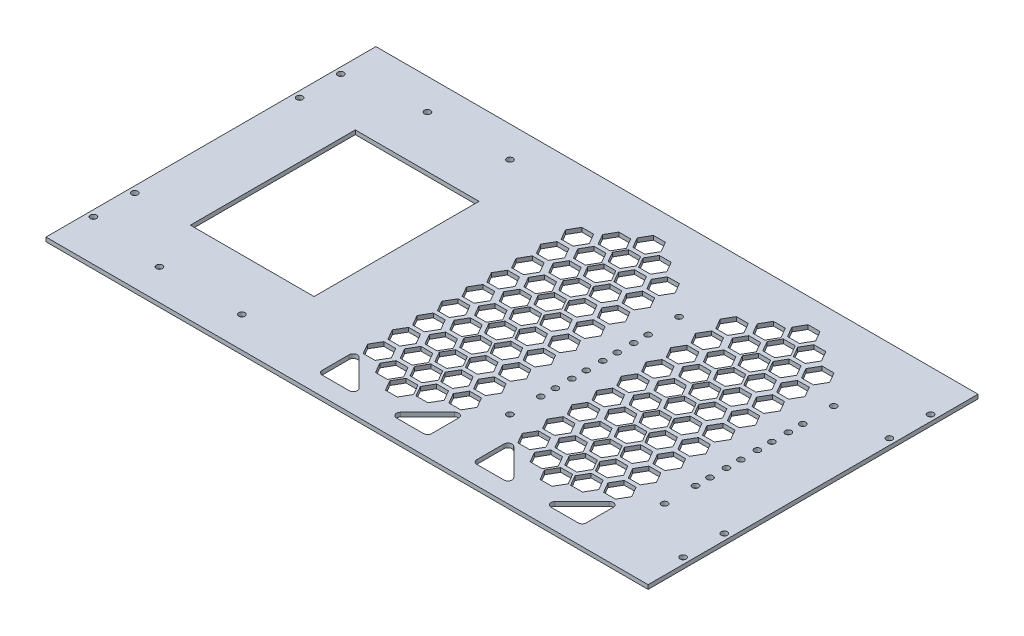
SolidWorks part; units mm, degrees
material "Thornel Mat VMA"
ref_plane "前视基准面" through (0, 0, 0) normal (0, 0, 1) x (1, 0, 0)
ref_plane "上视基准面" through (0, 0, 0) normal (0, 1, 0) x (1, 0, 0)
ref_plane "右视基准面" through (0, 0, 0) normal (1, 0, 0) x (0, 0, -1)
sketch "草图1" plane through (0, 0, 0) normal (0, 1, 0) x (1, 0, 0)
  line L0 (3, 40) -> (3, 20) construction
  line L1 (0, 0) -> (292, 0)
  line L2 (0, 0) -> (0, 160)
  line L3 (0, 160) -> (292, 160)
  line L4 (292, 0) -> (292, 160)
  line L5 (3, 140) -> (3, 120) construction
  line L6 (146, 160) -> (146, 0) construction
  line L7 (289, 40) -> (289, 20) construction
  line L8 (289, 140) -> (289, 120) construction
  line L9 (0, 80) -> (30, 80) construction
  line L10 (30, 120) -> (90, 120)
  line L11 (30, 120) -> (30, 40)
  line L12 (30, 40) -> (90, 40)
  line L13 (90, 120) -> (90, 40)
  line L14 (197, 120) -> (252, 120) construction
  line L15 (187, 120) -> (262, 120) construction
  line L16 (187, 120) -> (187, 98) construction
  line L17 (187, 98) -> (262, 98) construction
  line L18 (262, 120) -> (262, 98) construction
  line L19 (40, 145) -> (80, 145) construction
  line L20 (40, 145) -> (40, 15) construction
  line L21 (40, 15) -> (80, 15) construction
  line L22 (80, 145) -> (80, 15) construction
  line L27 (197, 124) -> (252, 124)
  line L28 (197, 116) -> (252, 116)
  line L29 (197, 101) -> (252, 101)
  line L30 (197, 109) -> (252, 109)
  line L31 (197, 105) -> (252, 105) construction
  line L32 (197, 86) -> (252, 86)
  line L33 (197, 94) -> (252, 94)
  line L34 (197, 90) -> (252, 90) construction
  line L35 (197, 71) -> (252, 71)
  line L36 (197, 79) -> (252, 79)
  line L37 (197, 75) -> (252, 75) construction
  line L38 (197, 56) -> (252, 56)
  line L39 (197, 64) -> (252, 64)
  line L40 (197, 60) -> (252, 60) construction
  line L41 (197, 45) -> (252, 45) construction
  line L42 (197, 49) -> (252, 49)
  line L43 (197, 41) -> (252, 41)
  line L44 (197, 30) -> (252, 30) construction
  line L45 (197, 34) -> (252, 34)
  line L46 (197, 26) -> (252, 26)
  line L47 (118.5, 116) -> (173.5, 116)
  line L48 (118.5, 124) -> (173.5, 124)
  line L49 (118.5, 109) -> (173.5, 109)
  line L50 (118.5, 101) -> (173.5, 101)
  line L51 (118.5, 94) -> (173.5, 94)
  line L52 (118.5, 86) -> (173.5, 86)
  line L53 (118.5, 79) -> (173.5, 79)
  line L54 (118.5, 71) -> (173.5, 71)
  line L55 (118.5, 64) -> (173.5, 64)
  line L56 (118.5, 56) -> (173.5, 56)
  line L57 (118.5, 49) -> (173.5, 49)
  line L58 (118.5, 41) -> (173.5, 41)
  line L59 (118.5, 34) -> (173.5, 34)
  line L60 (118.5, 26) -> (173.5, 26)
  line L61 (118.5, 120) -> (173.5, 120) construction
  line L62 (118.5, 105) -> (173.5, 105) construction
  line L63 (118.5, 90) -> (173.5, 90) construction
  line L64 (118.5, 75) -> (173.5, 75) construction
  line L65 (118.5, 60) -> (173.5, 60) construction
  line L66 (118.5, 45) -> (173.5, 45) construction
  line L67 (118.5, 30) -> (173.5, 30) construction
  circle A0 centre (3, 140) radius 1.5
  circle A1 centre (3, 120) radius 1.5
  circle A2 centre (3, 40) radius 1.5
  circle A3 centre (3, 20) radius 1.5
  circle A4 centre (289, 20) radius 1.5
  circle A5 centre (289, 40) radius 1.5
  circle A6 centre (289, 120) radius 1.5
  circle A7 centre (289, 140) radius 1.5
  circle A8 centre (187, 120) radius 1.5
  circle A9 centre (262, 120) radius 1.5
  circle A10 centre (262, 98) radius 1.5
  circle A11 centre (187, 98) radius 1.5
  circle A12 centre (187, 105) radius 1.5
  circle A13 centre (262, 105) radius 1.5
  circle A14 centre (187, 83) radius 1.5
  circle A15 centre (262, 83) radius 1.5
  circle A16 centre (187, 90) radius 1.5
  circle A17 centre (262, 90) radius 1.5
  circle A18 centre (187, 68) radius 1.5
  circle A19 centre (262, 68) radius 1.5
  circle A20 centre (187, 75) radius 1.5
  circle A21 centre (262, 75) radius 1.5
  circle A22 centre (187, 53) radius 1.5
  circle A23 centre (262, 53) radius 1.5
  circle A24 centre (187, 60) radius 1.5
  circle A25 centre (262, 60) radius 1.5
  circle A26 centre (187, 38) radius 1.5
  circle A27 centre (262, 38) radius 1.5
  circle A28 centre (40, 145) radius 1.5
  circle A29 centre (80, 145) radius 1.5
  circle A30 centre (40, 15) radius 1.5
  circle A31 centre (80, 15) radius 1.5
  arc A32 (197, 124) -> (197, 116) centre (197, 120) ccw
  arc A33 (252, 116) -> (252, 124) centre (252, 120) ccw
  arc A34 (197, 109) -> (197, 101) centre (197, 105) ccw
  arc A35 (252, 101) -> (252, 109) centre (252, 105) ccw
  arc A36 (197, 94) -> (197, 86) centre (197, 90) ccw
  arc A37 (252, 86) -> (252, 94) centre (252, 90) ccw
  arc A38 (197, 79) -> (197, 71) centre (197, 75) ccw
  arc A39 (252, 71) -> (252, 79) centre (252, 75) ccw
  arc A40 (197, 64) -> (197, 56) centre (197, 60) ccw
  arc A41 (252, 56) -> (252, 64) centre (252, 60) ccw
  arc A42 (197, 49) -> (197, 41) centre (197, 45) ccw
  arc A43 (252, 41) -> (252, 49) centre (252, 45) ccw
  arc A44 (197, 34) -> (197, 26) centre (197, 30) ccw
  arc A45 (252, 26) -> (252, 34) centre (252, 30) ccw
  arc A46 (118.5, 124) -> (118.5, 116) centre (118.5, 120) ccw
  arc A47 (173.5, 116) -> (173.5, 124) centre (173.5, 120) ccw
  arc A48 (173.5, 101) -> (173.5, 109) centre (173.5, 105) ccw
  arc A49 (118.5, 109) -> (118.5, 101) centre (118.5, 105) ccw
  arc A50 (173.5, 86) -> (173.5, 94) centre (173.5, 90) ccw
  arc A51 (118.5, 94) -> (118.5, 86) centre (118.5, 90) ccw
  arc A52 (173.5, 71) -> (173.5, 79) centre (173.5, 75) ccw
  arc A53 (118.5, 79) -> (118.5, 71) centre (118.5, 75) ccw
  arc A54 (173.5, 56) -> (173.5, 64) centre (173.5, 60) ccw
  arc A55 (118.5, 64) -> (118.5, 56) centre (118.5, 60) ccw
  arc A56 (173.5, 41) -> (173.5, 49) centre (173.5, 45) ccw
  arc A57 (118.5, 49) -> (118.5, 41) centre (118.5, 45) ccw
  arc A58 (173.5, 26) -> (173.5, 34) centre (173.5, 30) ccw
  arc A59 (118.5, 34) -> (118.5, 26) centre (118.5, 30) ccw
  point P79 (224.5, 120)
  point P89 (224.5, 105)
  point P96 (224.5, 90)
  point P103 (224.5, 75)
  point P110 (224.5, 60)
  point P117 (224.5, 45)
  point P123 (224.5, 30)
  point P129 (146, 120)
  point P137 (146, 105)
  point P144 (146, 90)
  point P151 (146, 75)
  point P158 (146, 60)
  point P165 (146, 45)
  point P171 (146, 30)
  dimension "D3" = 20
  dimension "D5" = 3
  dimension "D7" = 20
  dimension "D14" = 3
  dimension "D23" = 3
  dimension "D26" = 4
  dimension "D1" = 292
  dimension "D2" = 160
  dimension "D4" = 3
  dimension "D6" = 20
  dimension "D8" = 20
  dimension "D9" = 80
  dimension "D10" = 60
  dimension "D11" = 30
  dimension "D12" = 22
  dimension "D13" = 75
  dimension "D15" = 40
  dimension "D16" = 30
  dimension "D18" = 15
  dimension "D19" = 15
  dimension "D20" = 15
  dimension "D21" = 10
  dimension "D22" = 10
  dimension "D24" = 10
  dimension "D25" = 10
  dimension "D28" = 15
  dimension "D17" = 5
  dimension "D27" = 3
  dimension "D29" = 2
extrude "凸台-拉伸1" add sketch "草图1" along normal blind 2
sketch "草图2" plane through (0, 2, 0) normal (0, 1, 0) x (1, 0, 0)
  line L0 (107.3245, 140.5648) -> (107.3245, 18.8458)
  line L1 (107.3245, 18.8458) -> (180.5072, 18.8458)
  line L2 (180.5072, 18.8458) -> (180.5072, 140.5648)
  line L3 (180.5072, 140.5648) -> (107.3245, 140.5648)
  line L5 (190.3083, 128.6312) -> (259.3392, 128.6312)
  line L6 (190.3083, 128.6312) -> (190.3083, 23.2576)
  line L7 (190.3083, 23.2576) -> (259.3392, 23.2576)
  line L8 (259.3392, 128.6312) -> (259.3392, 23.2576)
extrude "凸台-拉伸2" add sketch "草图2" against normal up to surface (2 mm away) up to face at (40, 0, -13.5)
sketch "草图3" plane through (0, 2, 0) normal (0, 1, 0) x (1, 0, 0)
  line L0 (187, 120) -> (262, 120) construction
  line L1 (230.2735, 143) -> (227.3868, 148)
  line L2 (227.3868, 148) -> (221.6132, 148)
  line L3 (221.6132, 148) -> (218.7265, 143)
  line L4 (218.7265, 143) -> (221.6132, 138)
  line L5 (221.6132, 138) -> (227.3868, 138)
  line L6 (227.3868, 138) -> (230.2735, 143)
  line L7 (240.0885, 136) -> (237.2017, 141)
  line L8 (237.2017, 141) -> (231.4282, 141)
  line L9 (231.4282, 141) -> (228.5415, 136)
  line L10 (228.5415, 136) -> (231.4282, 131)
  line L11 (231.4282, 131) -> (237.2017, 131)
  line L12 (237.2017, 131) -> (240.0885, 136)
  line L19 (224.5, 120) -> (224.5, 160) construction
  line L20 (292, 160) -> (0, 160) construction
  line L21 (211.7983, 131) -> (208.9115, 136)
  line L22 (217.5718, 131) -> (211.7983, 131)
  line L23 (220.4585, 136) -> (217.5718, 131)
  line L24 (217.5718, 141) -> (220.4585, 136)
  line L25 (211.7983, 141) -> (217.5718, 141)
  line L26 (208.9115, 136) -> (211.7983, 141)
  line L27 (230.2735, 131) -> (227.3868, 136)
  line L28 (227.3868, 136) -> (221.6132, 136)
  line L29 (221.6132, 136) -> (218.7265, 131)
  line L30 (218.7265, 131) -> (221.6132, 126)
  line L31 (221.6132, 126) -> (227.3868, 126)
  line L32 (227.3868, 126) -> (230.2735, 131)
  line L33 (211.7983, 119) -> (208.9115, 124)
  line L34 (208.9115, 124) -> (211.7983, 129)
  line L35 (211.7983, 129) -> (217.5718, 129)
  line L36 (217.5718, 129) -> (220.4585, 124)
  line L37 (220.4585, 124) -> (217.5718, 119)
  line L38 (217.5718, 119) -> (211.7983, 119)
  line L39 (240.0885, 124) -> (237.2017, 129)
  line L40 (237.2017, 129) -> (231.4282, 129)
  line L41 (231.4282, 129) -> (228.5415, 124)
  line L42 (228.5415, 124) -> (231.4282, 119)
  line L43 (231.4282, 119) -> (237.2017, 119)
  line L44 (237.2017, 119) -> (240.0885, 124)
  line L45 (230.2735, 119) -> (227.3868, 124)
  line L46 (227.3868, 124) -> (221.6132, 124)
  line L47 (221.6132, 124) -> (218.7265, 119)
  line L48 (218.7265, 119) -> (221.6132, 114)
  line L49 (221.6132, 114) -> (227.3868, 114)
  line L50 (227.3868, 114) -> (230.2735, 119)
  line L51 (211.7983, 107) -> (208.9115, 112)
  line L52 (208.9115, 112) -> (211.7983, 117)
  line L53 (211.7983, 117) -> (217.5718, 117)
  line L54 (217.5718, 117) -> (220.4585, 112)
  line L55 (220.4585, 112) -> (217.5718, 107)
  line L56 (217.5718, 107) -> (211.7983, 107)
  line L57 (240.0885, 112) -> (237.2017, 117)
  line L58 (237.2017, 117) -> (231.4282, 117)
  line L59 (231.4282, 117) -> (228.5415, 112)
  line L60 (228.5415, 112) -> (231.4282, 107)
  line L61 (231.4282, 107) -> (237.2017, 107)
  line L62 (237.2017, 107) -> (240.0885, 112)
  line L63 (230.2735, 107) -> (227.3868, 112)
  line L64 (227.3868, 112) -> (221.6132, 112)
  line L65 (221.6132, 112) -> (218.7265, 107)
  line L66 (218.7265, 107) -> (221.6132, 102)
  line L67 (221.6132, 102) -> (227.3868, 102)
  line L68 (227.3868, 102) -> (230.2735, 107)
  line L69 (211.7983, 95) -> (208.9115, 100)
  line L70 (208.9115, 100) -> (211.7983, 105)
  line L71 (211.7983, 105) -> (217.5718, 105)
  line L72 (217.5718, 105) -> (220.4585, 100)
  line L73 (220.4585, 100) -> (217.5718, 95)
  line L74 (217.5718, 95) -> (211.7983, 95)
  line L75 (240.0885, 100) -> (237.2017, 105)
  line L76 (237.2017, 105) -> (231.4282, 105)
  line L77 (231.4282, 105) -> (228.5415, 100)
  line L78 (228.5415, 100) -> (231.4282, 95)
  line L79 (231.4282, 95) -> (237.2017, 95)
  line L80 (237.2017, 95) -> (240.0885, 100)
  line L81 (230.2735, 95) -> (227.3868, 100)
  line L82 (227.3868, 100) -> (221.6132, 100)
  line L83 (221.6132, 100) -> (218.7265, 95)
  line L84 (218.7265, 95) -> (221.6132, 90)
  line L85 (221.6132, 90) -> (227.3868, 90)
  line L86 (227.3868, 90) -> (230.2735, 95)
  line L87 (211.7983, 83) -> (208.9115, 88)
  line L88 (208.9115, 88) -> (211.7983, 93)
  line L89 (211.7983, 93) -> (217.5718, 93)
  line L90 (217.5718, 93) -> (220.4585, 88)
  line L91 (220.4585, 88) -> (217.5718, 83)
  line L92 (217.5718, 83) -> (211.7983, 83)
  line L93 (240.0885, 88) -> (237.2017, 93)
  line L94 (237.2017, 93) -> (231.4282, 93)
  line L95 (231.4282, 93) -> (228.5415, 88)
  line L96 (228.5415, 88) -> (231.4282, 83)
  line L97 (231.4282, 83) -> (237.2017, 83)
  line L98 (237.2017, 83) -> (240.0885, 88)
  line L99 (230.2735, 83) -> (227.3868, 88)
  line L100 (227.3868, 88) -> (221.6132, 88)
  line L101 (221.6132, 88) -> (218.7265, 83)
  line L102 (218.7265, 83) -> (221.6132, 78)
  line L103 (221.6132, 78) -> (227.3868, 78)
  line L104 (227.3868, 78) -> (230.2735, 83)
  line L105 (211.7983, 71) -> (208.9115, 76)
  line L106 (208.9115, 76) -> (211.7983, 81)
  line L107 (211.7983, 81) -> (217.5718, 81)
  line L108 (217.5718, 81) -> (220.4585, 76)
  line L109 (220.4585, 76) -> (217.5718, 71)
  line L110 (217.5718, 71) -> (211.7983, 71)
  line L111 (240.0885, 76) -> (237.2017, 81)
  line L112 (237.2017, 81) -> (231.4282, 81)
  line L113 (231.4282, 81) -> (228.5415, 76)
  line L114 (228.5415, 76) -> (231.4282, 71)
  line L115 (231.4282, 71) -> (237.2017, 71)
  line L116 (237.2017, 71) -> (240.0885, 76)
  line L117 (230.2735, 71) -> (227.3868, 76)
  line L118 (227.3868, 76) -> (221.6132, 76)
  line L119 (221.6132, 76) -> (218.7265, 71)
  line L120 (218.7265, 71) -> (221.6132, 66)
  line L121 (221.6132, 66) -> (227.3868, 66)
  line L122 (227.3868, 66) -> (230.2735, 71)
  line L123 (211.7983, 59) -> (208.9115, 64)
  line L124 (208.9115, 64) -> (211.7983, 69)
  line L125 (211.7983, 69) -> (217.5718, 69)
  line L126 (217.5718, 69) -> (220.4585, 64)
  line L127 (220.4585, 64) -> (217.5718, 59)
  line L128 (217.5718, 59) -> (211.7983, 59)
  line L129 (240.0885, 64) -> (237.2017, 69)
  line L130 (237.2017, 69) -> (231.4282, 69)
  line L131 (231.4282, 69) -> (228.5415, 64)
  line L132 (228.5415, 64) -> (231.4282, 59)
  line L133 (231.4282, 59) -> (237.2017, 59)
  line L134 (237.2017, 59) -> (240.0885, 64)
  line L135 (230.2735, 59) -> (227.3868, 64)
  line L136 (227.3868, 64) -> (221.6132, 64)
  line L137 (221.6132, 64) -> (218.7265, 59)
  line L138 (218.7265, 59) -> (221.6132, 54)
  line L139 (221.6132, 54) -> (227.3868, 54)
  line L140 (227.3868, 54) -> (230.2735, 59)
  line L141 (211.7983, 47) -> (208.9115, 52)
  line L142 (208.9115, 52) -> (211.7983, 57)
  line L143 (211.7983, 57) -> (217.5718, 57)
  line L144 (217.5718, 57) -> (220.4585, 52)
  line L145 (220.4585, 52) -> (217.5718, 47)
  line L146 (217.5718, 47) -> (211.7983, 47)
  line L147 (240.0885, 52) -> (237.2017, 57)
  line L148 (237.2017, 57) -> (231.4282, 57)
  line L149 (231.4282, 57) -> (228.5415, 52)
  line L150 (228.5415, 52) -> (231.4282, 47)
  line L151 (231.4282, 47) -> (237.2017, 47)
  line L152 (237.2017, 47) -> (240.0885, 52)
  line L153 (230.2735, 47) -> (227.3868, 52)
  line L154 (227.3868, 52) -> (221.6132, 52)
  line L155 (221.6132, 52) -> (218.7265, 47)
  line L156 (218.7265, 47) -> (221.6132, 42)
  line L157 (221.6132, 42) -> (227.3868, 42)
  line L158 (227.3868, 42) -> (230.2735, 47)
  line L159 (211.7983, 35) -> (208.9115, 40)
  line L160 (208.9115, 40) -> (211.7983, 45)
  line L161 (211.7983, 45) -> (217.5718, 45)
  line L162 (217.5718, 45) -> (220.4585, 40)
  line L163 (220.4585, 40) -> (217.5718, 35)
  line L164 (217.5718, 35) -> (211.7983, 35)
  line L165 (240.0885, 40) -> (237.2017, 45)
  line L166 (237.2017, 45) -> (231.4282, 45)
  line L167 (231.4282, 45) -> (228.5415, 40)
  line L168 (228.5415, 40) -> (231.4282, 35)
  line L169 (231.4282, 35) -> (237.2017, 35)
  line L170 (237.2017, 35) -> (240.0885, 40)
  line L171 (230.2735, 35) -> (227.3868, 40)
  line L172 (227.3868, 40) -> (221.6132, 40)
  line L173 (221.6132, 40) -> (218.7265, 35)
  line L174 (218.7265, 35) -> (221.6132, 30)
  line L175 (221.6132, 30) -> (227.3868, 30)
  line L176 (227.3868, 30) -> (230.2735, 35)
  line L177 (211.7983, 23) -> (208.9115, 28)
  line L178 (208.9115, 28) -> (211.7983, 33)
  line L179 (211.7983, 33) -> (217.5718, 33)
  line L180 (217.5718, 33) -> (220.4585, 28)
  line L181 (220.4585, 28) -> (217.5718, 23)
  line L182 (217.5718, 23) -> (211.7983, 23)
  line L183 (240.0885, 28) -> (237.2017, 33)
  line L184 (237.2017, 33) -> (231.4282, 33)
  line L185 (231.4282, 33) -> (228.5415, 28)
  line L186 (228.5415, 28) -> (231.4282, 23)
  line L187 (231.4282, 23) -> (237.2017, 23)
  line L188 (237.2017, 23) -> (240.0885, 28)
  line L189 (242.3979, 124) -> (239.5111, 129)
  line L190 (209.4889, 129) -> (206.6021, 134)
  line L191 (206.6021, 134) -> (200.8286, 134)
  line L192 (200.8286, 134) -> (197.9419, 129)
  line L193 (197.9419, 129) -> (200.8286, 124)
  line L194 (200.8286, 124) -> (206.6021, 124)
  line L195 (206.6021, 124) -> (209.4889, 129)
  line L196 (248.1714, 124) -> (242.3979, 124)
  line L197 (251.0581, 129) -> (248.1714, 124)
  line L198 (248.1714, 134) -> (251.0581, 129)
  line L199 (242.3979, 134) -> (248.1714, 134)
  line L200 (239.5111, 129) -> (242.3979, 134)
  line L201 (209.4889, 117) -> (206.6021, 122)
  line L202 (206.6021, 122) -> (200.8286, 122)
  line L203 (200.8286, 122) -> (197.9419, 117)
  line L204 (197.9419, 117) -> (200.8286, 112)
  line L205 (200.8286, 112) -> (206.6021, 112)
  line L206 (206.6021, 112) -> (209.4889, 117)
  line L207 (242.3979, 112) -> (239.5111, 117)
  line L208 (239.5111, 117) -> (242.3979, 122)
  line L209 (242.3979, 122) -> (248.1714, 122)
  line L210 (248.1714, 122) -> (251.0581, 117)
  line L211 (251.0581, 117) -> (248.1714, 112)
  line L212 (248.1714, 112) -> (242.3979, 112)
  line L213 (209.4889, 105) -> (206.6021, 110)
  line L214 (206.6021, 110) -> (200.8286, 110)
  line L215 (200.8286, 110) -> (197.9419, 105)
  line L216 (197.9419, 105) -> (200.8286, 100)
  line L217 (200.8286, 100) -> (206.6021, 100)
  line L218 (206.6021, 100) -> (209.4889, 105)
  line L219 (242.3979, 100) -> (239.5111, 105)
  line L220 (239.5111, 105) -> (242.3979, 110)
  line L221 (242.3979, 110) -> (248.1714, 110)
  line L222 (248.1714, 110) -> (251.0581, 105)
  line L223 (251.0581, 105) -> (248.1714, 100)
  line L224 (248.1714, 100) -> (242.3979, 100)
  line L225 (209.4889, 93) -> (206.6021, 98)
  line L226 (206.6021, 98) -> (200.8286, 98)
  line L227 (200.8286, 98) -> (197.9419, 93)
  line L228 (197.9419, 93) -> (200.8286, 88)
  line L229 (200.8286, 88) -> (206.6021, 88)
  line L230 (206.6021, 88) -> (209.4889, 93)
  line L231 (242.3979, 88) -> (239.5111, 93)
  line L232 (239.5111, 93) -> (242.3979, 98)
  line L233 (242.3979, 98) -> (248.1714, 98)
  line L234 (248.1714, 98) -> (251.0581, 93)
  line L235 (251.0581, 93) -> (248.1714, 88)
  line L236 (248.1714, 88) -> (242.3979, 88)
  line L237 (209.4889, 81) -> (206.6021, 86)
  line L238 (206.6021, 86) -> (200.8286, 86)
  line L239 (200.8286, 86) -> (197.9419, 81)
  line L240 (197.9419, 81) -> (200.8286, 76)
  line L241 (200.8286, 76) -> (206.6021, 76)
  line L242 (206.6021, 76) -> (209.4889, 81)
  line L243 (242.3979, 76) -> (239.5111, 81)
  line L244 (239.5111, 81) -> (242.3979, 86)
  line L245 (242.3979, 86) -> (248.1714, 86)
  line L246 (248.1714, 86) -> (251.0581, 81)
  line L247 (251.0581, 81) -> (248.1714, 76)
  line L248 (248.1714, 76) -> (242.3979, 76)
  line L249 (209.4889, 69) -> (206.6021, 74)
  line L250 (206.6021, 74) -> (200.8286, 74)
  line L251 (200.8286, 74) -> (197.9419, 69)
  line L252 (197.9419, 69) -> (200.8286, 64)
  line L253 (200.8286, 64) -> (206.6021, 64)
  line L254 (206.6021, 64) -> (209.4889, 69)
  line L255 (242.3979, 64) -> (239.5111, 69)
  line L256 (239.5111, 69) -> (242.3979, 74)
  line L257 (242.3979, 74) -> (248.1714, 74)
  line L258 (248.1714, 74) -> (251.0581, 69)
  line L259 (251.0581, 69) -> (248.1714, 64)
  line L260 (248.1714, 64) -> (242.3979, 64)
  line L261 (209.4889, 57) -> (206.6021, 62)
  line L262 (206.6021, 62) -> (200.8286, 62)
  line L263 (200.8286, 62) -> (197.9419, 57)
  line L264 (197.9419, 57) -> (200.8286, 52)
  line L265 (200.8286, 52) -> (206.6021, 52)
  line L266 (206.6021, 52) -> (209.4889, 57)
  line L267 (242.3979, 52) -> (239.5111, 57)
  line L268 (239.5111, 57) -> (242.3979, 62)
  line L269 (242.3979, 62) -> (248.1714, 62)
  line L270 (248.1714, 62) -> (251.0581, 57)
  line L271 (251.0581, 57) -> (248.1714, 52)
  line L272 (248.1714, 52) -> (242.3979, 52)
  line L273 (209.4889, 45) -> (206.6021, 50)
  line L274 (206.6021, 50) -> (200.8286, 50)
  line L275 (200.8286, 50) -> (197.9419, 45)
  line L276 (197.9419, 45) -> (200.8286, 40)
  line L277 (200.8286, 40) -> (206.6021, 40)
  line L278 (206.6021, 40) -> (209.4889, 45)
  line L279 (242.3979, 40) -> (239.5111, 45)
  line L280 (239.5111, 45) -> (242.3979, 50)
  line L281 (242.3979, 50) -> (248.1714, 50)
  line L282 (248.1714, 50) -> (251.0581, 45)
  line L283 (251.0581, 45) -> (248.1714, 40)
  line L284 (248.1714, 40) -> (242.3979, 40)
  line L285 (209.4889, 33) -> (206.6021, 38)
  line L286 (206.6021, 38) -> (200.8286, 38)
  line L287 (200.8286, 38) -> (197.9419, 33)
  line L288 (197.9419, 33) -> (200.8286, 28)
  line L289 (200.8286, 28) -> (206.6021, 28)
  line L290 (206.6021, 28) -> (209.4889, 33)
  line L291 (242.3979, 28) -> (239.5111, 33)
  line L292 (239.5111, 33) -> (242.3979, 38)
  line L293 (242.3979, 38) -> (248.1714, 38)
  line L294 (248.1714, 38) -> (251.0581, 33)
  line L295 (251.0581, 33) -> (248.1714, 28)
  line L296 (248.1714, 28) -> (242.3979, 28)
  line L297 (230.2735, 23) -> (227.3868, 28)
  line L298 (227.3868, 28) -> (221.6132, 28)
  line L299 (221.6132, 28) -> (218.7265, 23)
  line L300 (218.7265, 23) -> (221.6132, 18)
  line L301 (221.6132, 18) -> (227.3868, 18)
  line L302 (227.3868, 18) -> (230.2735, 23)
  line L303 (187, 120) -> (187, 160) construction
  line L304 (149.5, 120) -> (149.5, 160) construction
  line L305 (187, 120) -> (112, 120) construction
  line L306 (146.6132, 18) -> (143.7265, 23)
  line L307 (152.3868, 18) -> (146.6132, 18)
  line L308 (155.2735, 23) -> (152.3868, 18)
  line L309 (152.3868, 28) -> (155.2735, 23)
  line L310 (146.6132, 28) -> (152.3868, 28)
  line L311 (143.7265, 23) -> (146.6132, 28)
  line L312 (125.8286, 28) -> (131.6021, 28)
  line L313 (122.9419, 33) -> (125.8286, 28)
  line L314 (125.8286, 38) -> (122.9419, 33)
  line L315 (131.6021, 38) -> (125.8286, 38)
  line L316 (134.4889, 33) -> (131.6021, 38)
  line L317 (131.6021, 28) -> (134.4889, 33)
  line L318 (167.3979, 28) -> (164.5111, 33)
  line L319 (173.1714, 28) -> (167.3979, 28)
  line L320 (176.0581, 33) -> (173.1714, 28)
  line L321 (173.1714, 38) -> (176.0581, 33)
  line L322 (167.3979, 38) -> (173.1714, 38)
  line L323 (164.5111, 33) -> (167.3979, 38)
  line L324 (125.8286, 40) -> (131.6021, 40)
  line L325 (122.9419, 45) -> (125.8286, 40)
  line L326 (125.8286, 50) -> (122.9419, 45)
  line L327 (131.6021, 50) -> (125.8286, 50)
  line L328 (134.4889, 45) -> (131.6021, 50)
  line L329 (131.6021, 40) -> (134.4889, 45)
  line L330 (167.3979, 40) -> (164.5111, 45)
  line L331 (173.1714, 40) -> (167.3979, 40)
  line L332 (176.0581, 45) -> (173.1714, 40)
  line L333 (173.1714, 50) -> (176.0581, 45)
  line L334 (167.3979, 50) -> (173.1714, 50)
  line L335 (164.5111, 45) -> (167.3979, 50)
  line L336 (125.8286, 52) -> (131.6021, 52)
  line L337 (122.9419, 57) -> (125.8286, 52)
  line L338 (125.8286, 62) -> (122.9419, 57)
  line L339 (131.6021, 62) -> (125.8286, 62)
  line L340 (134.4889, 57) -> (131.6021, 62)
  line L341 (131.6021, 52) -> (134.4889, 57)
  line L342 (167.3979, 52) -> (164.5111, 57)
  line L343 (173.1714, 52) -> (167.3979, 52)
  line L344 (176.0581, 57) -> (173.1714, 52)
  line L345 (173.1714, 62) -> (176.0581, 57)
  line L346 (167.3979, 62) -> (173.1714, 62)
  line L347 (164.5111, 57) -> (167.3979, 62)
  line L348 (125.8286, 64) -> (131.6021, 64)
  line L349 (122.9419, 69) -> (125.8286, 64)
  line L350 (125.8286, 74) -> (122.9419, 69)
  line L351 (131.6021, 74) -> (125.8286, 74)
  line L352 (134.4889, 69) -> (131.6021, 74)
  line L353 (131.6021, 64) -> (134.4889, 69)
  line L354 (167.3979, 64) -> (164.5111, 69)
  line L355 (173.1714, 64) -> (167.3979, 64)
  line L356 (176.0581, 69) -> (173.1714, 64)
  line L357 (173.1714, 74) -> (176.0581, 69)
  line L358 (167.3979, 74) -> (173.1714, 74)
  line L359 (164.5111, 69) -> (167.3979, 74)
  line L360 (125.8286, 76) -> (131.6021, 76)
  line L361 (122.9419, 81) -> (125.8286, 76)
  line L362 (125.8286, 86) -> (122.9419, 81)
  line L363 (131.6021, 86) -> (125.8286, 86)
  line L364 (134.4889, 81) -> (131.6021, 86)
  line L365 (131.6021, 76) -> (134.4889, 81)
  line L366 (167.3979, 76) -> (164.5111, 81)
  line L367 (173.1714, 76) -> (167.3979, 76)
  line L368 (176.0581, 81) -> (173.1714, 76)
  line L369 (173.1714, 86) -> (176.0581, 81)
  line L370 (167.3979, 86) -> (173.1714, 86)
  line L371 (164.5111, 81) -> (167.3979, 86)
  line L372 (125.8286, 88) -> (131.6021, 88)
  line L373 (122.9419, 93) -> (125.8286, 88)
  line L374 (125.8286, 98) -> (122.9419, 93)
  line L375 (131.6021, 98) -> (125.8286, 98)
  line L376 (134.4889, 93) -> (131.6021, 98)
  line L377 (131.6021, 88) -> (134.4889, 93)
  line L378 (167.3979, 88) -> (164.5111, 93)
  line L379 (173.1714, 88) -> (167.3979, 88)
  line L380 (176.0581, 93) -> (173.1714, 88)
  line L381 (173.1714, 98) -> (176.0581, 93)
  line L382 (167.3979, 98) -> (173.1714, 98)
  line L383 (164.5111, 93) -> (167.3979, 98)
  line L384 (125.8286, 100) -> (131.6021, 100)
  line L385 (122.9419, 105) -> (125.8286, 100)
  line L386 (125.8286, 110) -> (122.9419, 105)
  line L387 (131.6021, 110) -> (125.8286, 110)
  line L388 (134.4889, 105) -> (131.6021, 110)
  line L389 (131.6021, 100) -> (134.4889, 105)
  line L390 (167.3979, 100) -> (164.5111, 105)
  line L391 (173.1714, 100) -> (167.3979, 100)
  line L392 (176.0581, 105) -> (173.1714, 100)
  line L393 (173.1714, 110) -> (176.0581, 105)
  line L394 (167.3979, 110) -> (173.1714, 110)
  line L395 (164.5111, 105) -> (167.3979, 110)
  line L396 (125.8286, 112) -> (131.6021, 112)
  line L397 (122.9419, 117) -> (125.8286, 112)
  line L398 (125.8286, 122) -> (122.9419, 117)
  line L399 (131.6021, 122) -> (125.8286, 122)
  line L400 (134.4889, 117) -> (131.6021, 122)
  line L401 (131.6021, 112) -> (134.4889, 117)
  line L402 (167.3979, 112) -> (164.5111, 117)
  line L403 (173.1714, 112) -> (167.3979, 112)
  line L404 (176.0581, 117) -> (173.1714, 112)
  line L405 (173.1714, 122) -> (176.0581, 117)
  line L406 (167.3979, 122) -> (173.1714, 122)
  line L407 (164.5111, 117) -> (167.3979, 122)
  line L408 (134.4889, 129) -> (131.6021, 134)
  line L409 (131.6021, 134) -> (125.8286, 134)
  line L410 (125.8286, 134) -> (122.9419, 129)
  line L411 (122.9419, 129) -> (125.8286, 124)
  line L412 (125.8286, 124) -> (131.6021, 124)
  line L413 (167.3979, 124) -> (164.5111, 129)
  line L414 (173.1714, 124) -> (167.3979, 124)
  line L415 (176.0581, 129) -> (173.1714, 124)
  line L416 (173.1714, 134) -> (176.0581, 129)
  line L417 (167.3979, 134) -> (173.1714, 134)
  line L418 (164.5111, 129) -> (167.3979, 134)
  line L419 (131.6021, 124) -> (134.4889, 129)
  line L420 (136.7983, 23) -> (133.9115, 28)
  line L421 (142.5718, 23) -> (136.7983, 23)
  line L422 (145.4585, 28) -> (142.5718, 23)
  line L423 (142.5718, 33) -> (145.4585, 28)
  line L424 (136.7983, 33) -> (142.5718, 33)
  line L425 (133.9115, 28) -> (136.7983, 33)
  line L426 (156.4282, 23) -> (162.2017, 23)
  line L427 (153.5415, 28) -> (156.4282, 23)
  line L428 (156.4282, 33) -> (153.5415, 28)
  line L429 (162.2017, 33) -> (156.4282, 33)
  line L430 (165.0885, 28) -> (162.2017, 33)
  line L431 (162.2017, 23) -> (165.0885, 28)
  line L432 (146.6132, 30) -> (143.7265, 35)
  line L433 (152.3868, 30) -> (146.6132, 30)
  line L434 (155.2735, 35) -> (152.3868, 30)
  line L435 (152.3868, 40) -> (155.2735, 35)
  line L436 (146.6132, 40) -> (152.3868, 40)
  line L437 (143.7265, 35) -> (146.6132, 40)
  line L438 (136.7983, 35) -> (133.9115, 40)
  line L439 (142.5718, 35) -> (136.7983, 35)
  line L440 (145.4585, 40) -> (142.5718, 35)
  line L441 (142.5718, 45) -> (145.4585, 40)
  line L442 (136.7983, 45) -> (142.5718, 45)
  line L443 (133.9115, 40) -> (136.7983, 45)
  line L444 (156.4282, 35) -> (162.2017, 35)
  line L445 (153.5415, 40) -> (156.4282, 35)
  line L446 (156.4282, 45) -> (153.5415, 40)
  line L447 (162.2017, 45) -> (156.4282, 45)
  line L448 (165.0885, 40) -> (162.2017, 45)
  line L449 (162.2017, 35) -> (165.0885, 40)
  line L450 (146.6132, 42) -> (143.7265, 47)
  line L451 (152.3868, 42) -> (146.6132, 42)
  line L452 (155.2735, 47) -> (152.3868, 42)
  line L453 (152.3868, 52) -> (155.2735, 47)
  line L454 (146.6132, 52) -> (152.3868, 52)
  line L455 (143.7265, 47) -> (146.6132, 52)
  line L456 (136.7983, 47) -> (133.9115, 52)
  line L457 (142.5718, 47) -> (136.7983, 47)
  line L458 (145.4585, 52) -> (142.5718, 47)
  line L459 (142.5718, 57) -> (145.4585, 52)
  line L460 (136.7983, 57) -> (142.5718, 57)
  line L461 (133.9115, 52) -> (136.7983, 57)
  line L462 (156.4282, 47) -> (162.2017, 47)
  line L463 (153.5415, 52) -> (156.4282, 47)
  line L464 (156.4282, 57) -> (153.5415, 52)
  line L465 (162.2017, 57) -> (156.4282, 57)
  line L466 (165.0885, 52) -> (162.2017, 57)
  line L467 (162.2017, 47) -> (165.0885, 52)
  line L468 (146.6132, 54) -> (143.7265, 59)
  line L469 (152.3868, 54) -> (146.6132, 54)
  line L470 (155.2735, 59) -> (152.3868, 54)
  line L471 (152.3868, 64) -> (155.2735, 59)
  line L472 (146.6132, 64) -> (152.3868, 64)
  line L473 (143.7265, 59) -> (146.6132, 64)
  line L474 (136.7983, 59) -> (133.9115, 64)
  line L475 (142.5718, 59) -> (136.7983, 59)
  line L476 (145.4585, 64) -> (142.5718, 59)
  line L477 (142.5718, 69) -> (145.4585, 64)
  line L478 (136.7983, 69) -> (142.5718, 69)
  line L479 (133.9115, 64) -> (136.7983, 69)
  line L480 (156.4282, 59) -> (162.2017, 59)
  line L481 (153.5415, 64) -> (156.4282, 59)
  line L482 (156.4282, 69) -> (153.5415, 64)
  line L483 (162.2017, 69) -> (156.4282, 69)
  line L484 (165.0885, 64) -> (162.2017, 69)
  line L485 (162.2017, 59) -> (165.0885, 64)
  line L486 (146.6132, 66) -> (143.7265, 71)
  line L487 (152.3868, 66) -> (146.6132, 66)
  line L488 (155.2735, 71) -> (152.3868, 66)
  line L489 (152.3868, 76) -> (155.2735, 71)
  line L490 (146.6132, 76) -> (152.3868, 76)
  line L491 (143.7265, 71) -> (146.6132, 76)
  line L492 (136.7983, 71) -> (133.9115, 76)
  line L493 (142.5718, 71) -> (136.7983, 71)
  line L494 (145.4585, 76) -> (142.5718, 71)
  line L495 (142.5718, 81) -> (145.4585, 76)
  line L496 (136.7983, 81) -> (142.5718, 81)
  line L497 (133.9115, 76) -> (136.7983, 81)
  line L498 (156.4282, 71) -> (162.2017, 71)
  line L499 (153.5415, 76) -> (156.4282, 71)
  line L500 (156.4282, 81) -> (153.5415, 76)
  line L501 (162.2017, 81) -> (156.4282, 81)
  line L502 (165.0885, 76) -> (162.2017, 81)
  line L503 (162.2017, 71) -> (165.0885, 76)
  line L504 (146.6132, 78) -> (143.7265, 83)
  line L505 (152.3868, 78) -> (146.6132, 78)
  line L506 (155.2735, 83) -> (152.3868, 78)
  line L507 (152.3868, 88) -> (155.2735, 83)
  line L508 (146.6132, 88) -> (152.3868, 88)
  line L509 (143.7265, 83) -> (146.6132, 88)
  line L510 (136.7983, 83) -> (133.9115, 88)
  line L511 (142.5718, 83) -> (136.7983, 83)
  line L512 (145.4585, 88) -> (142.5718, 83)
  line L513 (142.5718, 93) -> (145.4585, 88)
  line L514 (136.7983, 93) -> (142.5718, 93)
  line L515 (133.9115, 88) -> (136.7983, 93)
  line L516 (156.4282, 83) -> (162.2017, 83)
  line L517 (153.5415, 88) -> (156.4282, 83)
  line L518 (156.4282, 93) -> (153.5415, 88)
  line L519 (162.2017, 93) -> (156.4282, 93)
  line L520 (165.0885, 88) -> (162.2017, 93)
  line L521 (162.2017, 83) -> (165.0885, 88)
  line L522 (146.6132, 90) -> (143.7265, 95)
  line L523 (152.3868, 90) -> (146.6132, 90)
  line L524 (155.2735, 95) -> (152.3868, 90)
  line L525 (152.3868, 100) -> (155.2735, 95)
  line L526 (146.6132, 100) -> (152.3868, 100)
  line L527 (143.7265, 95) -> (146.6132, 100)
  line L528 (136.7983, 95) -> (133.9115, 100)
  line L529 (142.5718, 95) -> (136.7983, 95)
  line L530 (145.4585, 100) -> (142.5718, 95)
  line L531 (142.5718, 105) -> (145.4585, 100)
  line L532 (136.7983, 105) -> (142.5718, 105)
  line L533 (133.9115, 100) -> (136.7983, 105)
  line L534 (156.4282, 95) -> (162.2017, 95)
  line L535 (153.5415, 100) -> (156.4282, 95)
  line L536 (156.4282, 105) -> (153.5415, 100)
  line L537 (162.2017, 105) -> (156.4282, 105)
  line L538 (165.0885, 100) -> (162.2017, 105)
  line L539 (162.2017, 95) -> (165.0885, 100)
  line L540 (146.6132, 102) -> (143.7265, 107)
  line L541 (152.3868, 102) -> (146.6132, 102)
  line L542 (155.2735, 107) -> (152.3868, 102)
  line L543 (152.3868, 112) -> (155.2735, 107)
  line L544 (146.6132, 112) -> (152.3868, 112)
  line L545 (143.7265, 107) -> (146.6132, 112)
  line L546 (136.7983, 107) -> (133.9115, 112)
  line L547 (142.5718, 107) -> (136.7983, 107)
  line L548 (145.4585, 112) -> (142.5718, 107)
  line L549 (142.5718, 117) -> (145.4585, 112)
  line L550 (136.7983, 117) -> (142.5718, 117)
  line L551 (133.9115, 112) -> (136.7983, 117)
  line L552 (156.4282, 107) -> (162.2017, 107)
  line L553 (153.5415, 112) -> (156.4282, 107)
  line L554 (156.4282, 117) -> (153.5415, 112)
  line L555 (162.2017, 117) -> (156.4282, 117)
  line L556 (165.0885, 112) -> (162.2017, 117)
  line L557 (162.2017, 107) -> (165.0885, 112)
  line L558 (146.6132, 114) -> (143.7265, 119)
  line L559 (152.3868, 114) -> (146.6132, 114)
  line L560 (155.2735, 119) -> (152.3868, 114)
  line L561 (152.3868, 124) -> (155.2735, 119)
  line L562 (146.6132, 124) -> (152.3868, 124)
  line L563 (143.7265, 119) -> (146.6132, 124)
  line L564 (136.7983, 119) -> (133.9115, 124)
  line L565 (142.5718, 119) -> (136.7983, 119)
  line L566 (145.4585, 124) -> (142.5718, 119)
  line L567 (142.5718, 129) -> (145.4585, 124)
  line L568 (136.7983, 129) -> (142.5718, 129)
  line L569 (133.9115, 124) -> (136.7983, 129)
  line L570 (156.4282, 119) -> (162.2017, 119)
  line L571 (153.5415, 124) -> (156.4282, 119)
  line L572 (156.4282, 129) -> (153.5415, 124)
  line L573 (162.2017, 129) -> (156.4282, 129)
  line L574 (165.0885, 124) -> (162.2017, 129)
  line L575 (162.2017, 119) -> (165.0885, 124)
  line L576 (146.6132, 126) -> (143.7265, 131)
  line L577 (152.3868, 126) -> (146.6132, 126)
  line L578 (155.2735, 131) -> (152.3868, 126)
  line L579 (152.3868, 136) -> (155.2735, 131)
  line L580 (146.6132, 136) -> (152.3868, 136)
  line L581 (143.7265, 131) -> (146.6132, 136)
  line L582 (165.0885, 136) -> (162.2017, 141)
  line L583 (162.2017, 141) -> (156.4282, 141)
  line L584 (156.4282, 141) -> (153.5415, 136)
  line L585 (153.5415, 136) -> (156.4282, 131)
  line L586 (156.4282, 131) -> (162.2017, 131)
  line L587 (162.2017, 131) -> (165.0885, 136)
  line L588 (136.7983, 131) -> (133.9115, 136)
  line L589 (142.5718, 131) -> (136.7983, 131)
  line L590 (145.4585, 136) -> (142.5718, 131)
  line L591 (142.5718, 141) -> (145.4585, 136)
  line L592 (136.7983, 141) -> (142.5718, 141)
  line L593 (133.9115, 136) -> (136.7983, 141)
  line L594 (146.6132, 138) -> (143.7265, 143)
  line L595 (152.3868, 138) -> (146.6132, 138)
  line L596 (155.2735, 143) -> (152.3868, 138)
  line L597 (152.3868, 148) -> (155.2735, 143)
  line L598 (146.6132, 148) -> (152.3868, 148)
  line L599 (143.7265, 143) -> (146.6132, 148)
  line L600 (172.6439, 25.5) -> (159.5581, 12.4142)
  line L601 (160.9723, 9) -> (174.0581, 9)
  line L602 (176.0581, 11) -> (176.0581, 24.0858)
  line L603 (176.0581, 28.9142) -> (176.0581, 33) construction
  line L604 (0, 0) -> (292, 0) construction
  line L605 (213.0277, 9) -> (199.9419, 9)
  line L606 (201.3561, 25.5) -> (214.4419, 12.4142)
  line L607 (197.9419, 11) -> (197.9419, 24.0858)
  line L608 (247.6439, 25.5) -> (234.5581, 12.4142)
  line L609 (251.0581, 11) -> (251.0581, 24.0858)
  line L610 (235.9723, 9) -> (249.0581, 9)
  line L611 (138.0277, 9) -> (124.9419, 9)
  line L612 (126.3561, 25.5) -> (139.4419, 12.4142)
  line L613 (122.9419, 11) -> (122.9419, 24.0858)
  line L614 (230.2735, 83) -> (218.7265, 83) construction
  circle A0 centre (224.5, 143) radius 5 construction
  circle A1 centre (234.315, 136) radius 5 construction
  circle A2 centre (203.7154, 129) radius 5 construction
  circle A3 centre (170.2846, 129) radius 5 construction
  circle A4 centre (139.685, 136) radius 5 construction
  circle A5 centre (149.5, 143) radius 5 construction
  arc A6 (176.0581, 11) -> (174.0581, 9) centre (174.0581, 11) cw
  arc A7 (176.0581, 24.0858) -> (172.6439, 25.5) centre (174.0581, 24.0858) ccw
  arc A8 (160.9723, 9) -> (159.5581, 12.4142) centre (160.9723, 11) cw
  arc A9 (213.0277, 9) -> (214.4419, 12.4142) centre (213.0277, 11) ccw
  arc A10 (197.9419, 11) -> (199.9419, 9) centre (199.9419, 11) ccw
  arc A11 (197.9419, 24.0858) -> (201.3561, 25.5) centre (199.9419, 24.0858) cw
  arc A12 (235.9723, 9) -> (234.5581, 12.4142) centre (235.9723, 11) cw
  arc A13 (251.0581, 24.0858) -> (247.6439, 25.5) centre (249.0581, 24.0858) ccw
  arc A14 (251.0581, 11) -> (249.0581, 9) centre (249.0581, 11) cw
  arc A15 (138.0277, 9) -> (139.4419, 12.4142) centre (138.0277, 11) ccw
  arc A16 (122.9419, 11) -> (124.9419, 9) centre (124.9419, 11) ccw
  arc A17 (122.9419, 24.0858) -> (126.3561, 25.5) centre (124.9419, 24.0858) cw
  dimension "D16" = 2
  dimension "D1" = 10
  dimension "D2" = 10
  dimension "D3" = 10
  dimension "D4" = 17
  dimension "D5" = 2
  dimension "D6" = 2
  dimension "D7" = 2
  dimension "D8" = 10
  dimension "D9" = 2
  dimension "D10" = 2
  dimension "D12" = 2
  dimension "D14" = 2
  dimension "D15" = 45
  dimension "D17" = 9
  dimension "D18" = 16.5
  dimension "D11" = 9
  dimension "D13" = 2
extrude "切除-拉伸1" cut sketch "草图3" against normal blind 10
